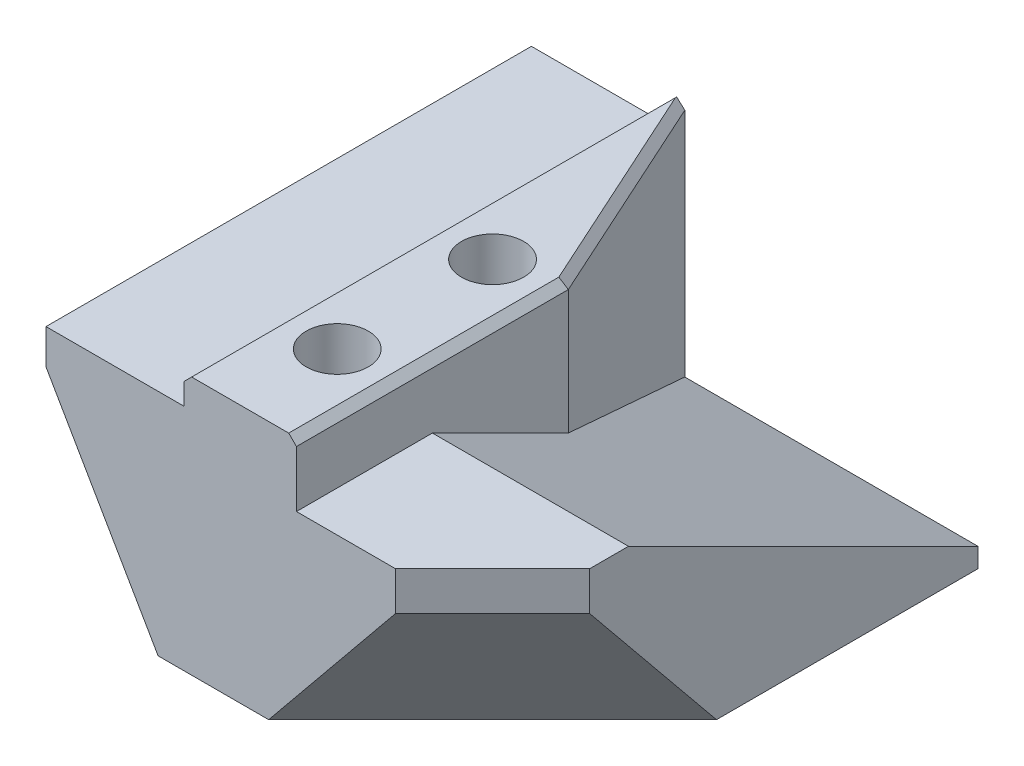
SolidWorks part; units mm, degrees
ref_plane "前视基准面" through (0, 0, 0) normal (0, 0, 1) x (1, 0, 0)
ref_plane "上视基准面" through (0, 0, 0) normal (0, 1, 0) x (1, 0, 0)
ref_plane "右视基准面" through (0, 0, 0) normal (1, 0, 0) x (0, 0, -1)
other "Configuration Table"
sketch "草图1" plane through (0, 0, 0) normal (0, 1, 0) x (1, 0, 0)
  line L1 (0, 0) -> (20, 0)
  line L2 (0, 0) -> (0, 20)
  line L3 (0, 20) -> (20, 20)
  line L4 (20, 0) -> (20, 20)
  dimension "D1" = 20
  dimension "D2" = 20
extrude "凸台-拉伸1" add sketch "草图1" along normal blind 4
sketch "草图2" plane through (0, 4, 0) normal (0, 1, 0) x (1, 0, 0)
  line L0 (0, 0) -> (20, 0) construction
  line L1 (0, 20) -> (12.9, 20)
  line L2 (0, 20) -> (0, 0)
  line L3 (0, 0) -> (12.9, 0)
  line L4 (12.9, 20) -> (12.9, 0)
  line L5 (20, 0) -> (20, 20) construction
  dimension "D1" = 7.1
extrude "凸台-拉伸2" add sketch "草图2" along normal blind 3.8
sketch "草图3" plane through (0, 0, 0) normal (0, -1, 0) x (-1, 0, 0)
  line L0 (0, 20) -> (0, 0) construction
  line L2 (0, 0) -> (-20, 0) construction
  circle A0 centre (-10, 5) radius 1.6
  circle A1 centre (-10, 13) radius 1.6
  dimension "D1" = 3.2
  dimension "D3" = 5
  dimension "D2" = 10
  dimension "D4" = 2
extrude "切除-拉伸1" cut sketch "草图3" against normal through all
sketch "草图4" plane through (0, 7.8, 0) normal (0, 1, 0) x (1, 0, 0)
  line L0 (12.9, 20) -> (0, 20) construction
  line L1 (7.1, 20) -> (12.9, 20)
  line L2 (7.1, 20) -> (7.1, 0)
  line L3 (7.1, 0) -> (12.9, 0)
  line L4 (12.9, 20) -> (12.9, 0)
  line L5 (0, 20) -> (0, 0) construction
  circle A0 centre (10, 13) radius 1.6
  circle A1 centre (10, 5) radius 1.6
  point P6 (10, 20)
  dimension "D1" = 5.8
  dimension "D2" = 10
extrude "凸台-拉伸3" add sketch "草图4" along normal blind 1.5
sketch "草图5" plane through (0, 0, 0) normal (0, -1, 0) x (-1, 0, 0)
  circle A0 centre (-10, 5) radius 3
  circle A1 centre (-10, 13) radius 3
  dimension "D1" = 6
  dimension "D2" = 6
extrude "切除-拉伸3" cut sketch "草图5" against normal blind 2.4
sketch "草图6" plane through (20, 0, 0) normal (1, 0, 0) x (0, 0, -1)
  line L1 (20, 0) -> (0, 0)
  line L2 (20, 0) -> (20, 4)
  line L3 (20, 4) -> (0, 4)
  line L4 (0, 0) -> (0, 4)
extrude "凸台-拉伸4" add sketch "草图6" along normal blind 3
sketch "草图7" plane through (0, 0, 0) normal (0, -1, 0) x (-1, 0, 0)
  line L1 (-23, 20) -> (0, 20)
  line L2 (-23, 20) -> (-23, 0)
  line L3 (-23, 0) -> (0, 0)
  line L4 (0, 20) -> (0, 0)
  circle A0 centre (-10, 13) radius 3
  circle A1 centre (-10, 5) radius 3
extrude "凸台-拉伸5" add sketch "草图7" along normal blind 4
sketch "草图9" plane through (0, 4, 0) normal (0, 1, 0) x (1, 0, 0)
  line L1 (23, 20) -> (12.9, 20)
  line L2 (23, 20) -> (23, 0)
  line L3 (23, 0) -> (12.9, 0)
  line L4 (12.9, 20) -> (12.9, 0)
extrude "凸台-拉伸6" add sketch "草图9" along normal blind 2
sketch "草图11" plane through (0, 0, -20) normal (0, 0, -1) x (-1, 0, 0)
  line L20 (-23, 6) -> (-23, -4)
  line L21 (-23, -4) -> (0, -4)
  line L22 (0, -4) -> (0, 7.8)
  line L23 (0, 7.8) -> (-7.1, 7.8)
  line L24 (-7.1, 7.8) -> (-7.1, 9.3)
  line L25 (-7.1, 9.3) -> (-12.9, 9.3)
  line L26 (-12.9, 9.3) -> (-12.9, 6)
  line L29 (-12.9, 6) -> (-23, 6)
  line L30 (-23, 6) -> (-23, -4)
  line L31 (-23, -4) -> (0, -4)
  line L32 (0, -4) -> (0, 7.8)
  line L33 (0, 7.8) -> (-7.1, 7.8)
  line L34 (-7.1, 7.8) -> (-7.1, 9.3)
  line L35 (-7.1, 9.3) -> (-12.9, 9.3)
  line L36 (-12.9, 9.3) -> (-12.9, 6)
  line L39 (-12.9, 6) -> (-23, 6)
  dimension "D1" = 0
extrude "凸台-拉伸7" add sketch "草图11" along normal blind 5
chamfer "倒角7" distance 10 angle 30 1 edges at (0, -4, -12.5) first distance on face at (0, 1.9, -12.5)
chamfer "倒角8" distance 5 angle 45 1 edges at (23, 1, 0)
chamfer "倒角9" distance 8 angle 30 1 edges at (20.5, -4, -2.5) first distance on face at (20.5, 1, -2.5)
sketch "草图15" plane through (23, 0, 0) normal (1, 0, 0) x (0, 0, -1)
  line L0 (25, -3) -> (25, 6)
  line L1 (25, 6) -> (25, -4) construction
  line L2 (25, 6) -> (7, 6)
  line L3 (25, 6) -> (0, 6) construction
  line L4 (7, 6) -> (25, -3)
  dimension "D1" = 9
  dimension "D2" = 18
extrude "切除-拉伸9" cut sketch "草图15" against normal up to surface (10.1 mm away) up to face at (12.9, 7.65, -12.5)
sketch "草图16" plane through (0, 9.3, 0) normal (0, 1, 0) x (1, 0, 0)
  line L0 (7.9, 25) -> (12.9, 25)
  line L1 (7.1, 25) -> (12.9, 25) construction
  line L2 (12.9, 7) -> (12.9, 25) construction
  line L3 (12.9, 0) -> (12.9, 25) construction
  line L4 (12.9, 25) -> (12.9, 14)
  line L5 (12.9, 14) -> (7.9, 25)
  dimension "D1" = 5
  dimension "D2" = 11
extrude "切除-拉伸10" cut sketch "草图16" against normal up to surface (6.8 mm away) up to face at (17.95, 1.5, -16)
chamfer "倒角10" distance 1.5 angle 45 2 edges at (10, 2.4, -14.6) (10, 2.4, -6.6)
chamfer "倒角11" distance 0.4 angle 45 3 edges at (10.4, 9.3, -19.5) (12.9, 9.3, -7) (7.1, 9.3, -12.5)
